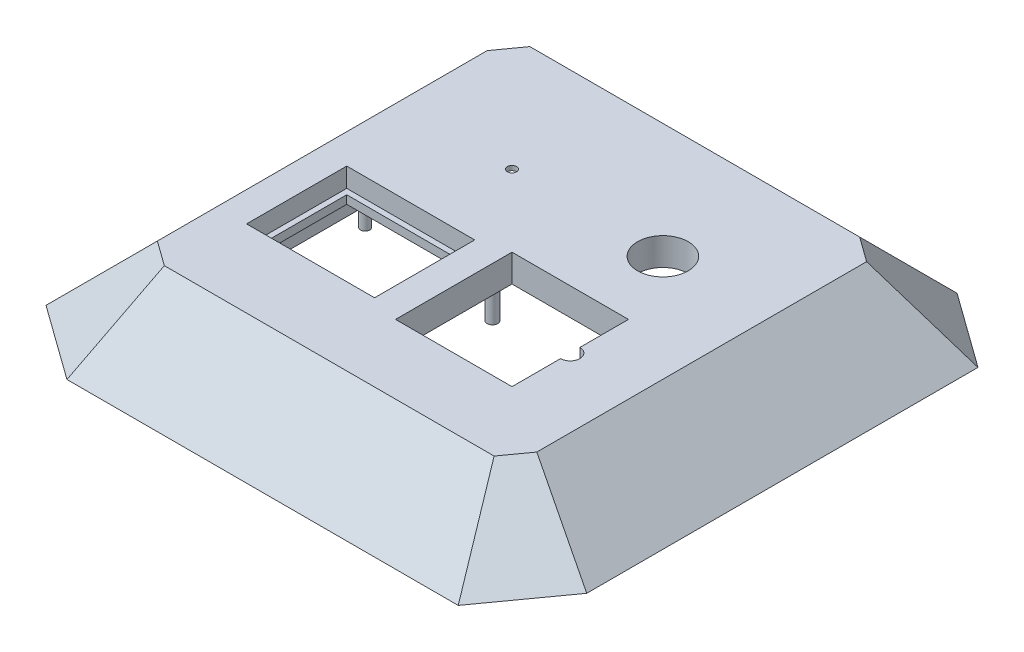
SolidWorks part; units mm, degrees
ref_plane "Front Plane" through (0, 0, 0) normal (0, 0, 1) x (1, 0, 0)
ref_plane "Top Plane" through (0, 0, 0) normal (0, 1, 0) x (1, 0, 0)
ref_plane "Right Plane" through (0, 0, 0) normal (1, 0, 0) x (0, 0, -1)
sketch "Sketch1" plane through (0, 0, 0) normal (0, 1, 0) x (1, 0, 0)
  line L0 (-47.3454, -21.7516) -> (37.6546, -21.7516)
  line L1 (37.6546, -21.7516) -> (49.3368, -5.5181)
  line L2 (49.3368, -5.5181) -> (49.3368, 79.4819)
  line L3 (49.3368, 79.4819) -> (33.1033, 91.1641)
  line L4 (33.1033, 91.1641) -> (-51.8967, 91.1641)
  line L5 (-51.8967, 91.1641) -> (-63.5789, 74.9306)
  line L6 (-63.5789, 74.9306) -> (-63.5789, -10.0694)
  line L7 (-63.5789, -10.0694) -> (-47.3454, -21.7516)
  dimension "D2" = 85
  dimension "D3" = 85
  dimension "D4" = 144.26
  dimension "D5" = 144.26
  dimension "D6" = 85
  dimension "D7" = 144.26
  dimension "D8" = 20
  dimension "D9" = 85
  dimension "D10" = 20
  dimension "D11" = 20
extrude "Boss-Extrude2" add sketch "Sketch1" along normal blind 16
sketch "Sketch4" plane through (0, 0, 0) normal (0, -1, 0) x (1, 0, 0)
  line L16 (-42.1868, 5.7516) -> (-47.5789, 1.8712)
  line L17 (-47.5789, 1.8712) -> (-47.5789, -69.772)
  line L18 (-47.5789, -69.772) -> (-43.6985, -75.1641)
  line L19 (-43.6985, -75.1641) -> (27.9447, -75.1641)
  line L20 (27.9447, -75.1641) -> (33.3368, -71.2838)
  line L21 (33.3368, -71.2838) -> (33.3368, 0.3594)
  line L22 (33.3368, 0.3594) -> (29.4564, 5.7516)
  line L23 (29.4564, 5.7516) -> (-42.1868, 5.7516)
  line L24 (-42.1868, 5.7516) -> (-47.5789, 1.8712)
  line L25 (-47.5789, 1.8712) -> (-47.5789, -69.772)
  line L26 (-47.5789, -69.772) -> (-43.6985, -75.1641)
  line L27 (-43.6985, -75.1641) -> (27.9447, -75.1641)
  line L28 (27.9447, -75.1641) -> (33.3368, -71.2838)
  line L29 (33.3368, -71.2838) -> (33.3368, 0.3594)
  line L30 (33.3368, 0.3594) -> (29.4564, 5.7516)
  line L31 (29.4564, 5.7516) -> (-42.1868, 5.7516)
  dimension "D1" = 16
chamfer "Chamfer1" distance 16 angle 45 8 edges at (-63.5789, 16, -32.4306) (-57.7378, 16, -83.0473) (-9.3967, 16, -91.1641) (41.22, 16, -85.323) (49.3368, 16, -36.9819) (43.4957, 16, 13.6348) (-4.8454, 16, 21.7516) (-55.4621, 16, 15.9105)
extrude "Cut-Extrude3" cut sketch "Sketch4" against normal blind 10
sketch "Sketch6" plane through (0, 16, 0) normal (0, 1, 0) x (1, 0, 0)
  line L0 (33.3368, -0.3594) -> (33.3368, 71.2838) construction
  line L1 (-6.9632, 34.5484) -> (18.3368, 34.5484)
  line L2 (-6.9632, 34.5484) -> (-6.9632, 9.2484)
  line L3 (-6.9632, 9.2484) -> (18.3368, 9.2484)
  line L4 (18.3368, 34.5484) -> (18.3368, 9.2484)
  line L5 (-42.1868, -5.7516) -> (29.4564, -5.7516) construction
  dimension "D1" = 25.3
  dimension "D2" = 25.3
  dimension "D3" = 15
  dimension "D4" = 15
extrude "Cut-Extrude4" cut sketch "Sketch6" against normal up to next
sketch "Sketch7" plane through (0, 10, 0) normal (0, -1, 0) x (1, 0, 0)
  line L0 (18.3368, -9.2484) -> (18.3368, -34.5484) construction
  circle A0 centre (18.3368, -21.8984) radius 2.0981
extrude "Cut-Extrude5" cut sketch "Sketch7" against normal up to next
sketch "Sketch8" plane through (0, 10, 0) normal (0, -1, 0) x (1, 0, 0)
  line L0 (-11.7632, -21.9984) -> (30.1662, -21.9984) construction
  line L1 (-11.7632, -8.8984) -> (24.2368, -8.8984)
  line L2 (-11.7632, -8.8984) -> (-11.7632, -35.0984)
  line L3 (-11.7632, -35.0984) -> (24.2368, -35.0984)
  line L4 (24.2368, -8.8984) -> (24.2368, -35.0984)
  line L5 (6.2368, -8.8984) -> (6.2368, -38.2867) construction
  line L6 (33.3368, -71.2838) -> (33.3368, 0.3594) construction
  line L7 (29.4564, 5.7516) -> (-42.1868, 5.7516) construction
  circle A0 centre (-9.2132, -11.4484) radius 1.15
  circle A1 centre (21.6868, -11.4484) radius 1.15
  circle A2 centre (21.6868, -32.5484) radius 1.15
  circle A3 centre (-9.2132, -32.5484) radius 1.15
  dimension "D3" = 2.3
  dimension "D4" = 2.55
  dimension "D5" = 2.55
  dimension "D6" = 9.1
  dimension "D1" = 36
  dimension "D2" = 26.2
  dimension "D7" = 14.65
extrude "Boss-Extrude3" add sketch "Sketch8" along normal blind 7 contours A0 | A1 | A2 | A3 region at (-9.2132, 10, -11.4484) region at (21.6868, 10, -11.4484) region at (21.6868, 10, -32.5484)
sketch "Sketch9" plane through (0, 10, 0) normal (0, -1, 0) x (1, 0, 0)
  line L2 (-47.5789, 1.8712) -> (-47.5789, -69.772) construction
  line L3 (-43.6985, -75.1641) -> (27.9447, -75.1641) construction
  circle A0 centre (-22.5789, -50.1641) radius 15.65
  dimension "D1" = 25
  dimension "D2" = 25
  dimension "D3" = 31.3
extrude "Cut-Extrude6" cut sketch "Sketch9" against normal blind 5
sketch "Sketch10" plane through (0, 15, 0) normal (0, -1, 0) x (1, 0, 0)
  circle A0 centre (-22.5789, -50.1641) radius 1
  dimension "D1" = 2
extrude "Cut-Extrude7" cut sketch "Sketch10" against normal up to next
sketch "Sketch11" plane through (0, 16, 0) normal (0, 1, 0) x (1, 0, 0)
  line L0 (-14.7144, 21.8984) -> (-6.9632, 21.8984) construction
  line L1 (-14.7144, 35.3984) -> (-39.7144, 35.3984)
  line L2 (-14.7144, 35.3984) -> (-14.7144, 8.3984)
  line L3 (-14.7144, 8.3984) -> (-39.7144, 8.3984)
  line L4 (-39.7144, 35.3984) -> (-39.7144, 8.3984)
  line L5 (-6.9632, 34.5484) -> (-6.9632, 9.2484) construction
  line L6 (-27.2144, 35.3984) -> (-27.2144, 2.0931) construction
  line L7 (-14.7144, 21.8984) -> (-44.3409, 21.8984) construction
  circle A0 centre (-37.5644, 33.2484) radius 1
  circle A1 centre (-16.8644, 33.2484) radius 1
  circle A2 centre (-16.8644, 10.5484) radius 1
  circle A3 centre (-37.5644, 10.5484) radius 1
  dimension "D3" = 2
  dimension "D4" = 2.15
  dimension "D5" = 2.15
  dimension "D1" = 25
  dimension "D2" = 27
extrude "Boss-Extrude4" add sketch "Sketch11" against normal blind 10 contours A0 | A1 | A2 | A3
sketch "Sketch12" plane through (0, 16, 0) normal (0, 1, 0) x (1, 0, 0)
  line L0 (-14.7144, 35.3984) -> (-14.7144, 8.3984) construction
  line L1 (-39.9144, 31.5984) -> (-14.5144, 31.5984)
  line L2 (-39.9144, 31.5984) -> (-39.9144, 12.2384)
  line L3 (-39.9144, 12.2384) -> (-14.5144, 12.2384)
  line L4 (-14.5144, 31.5984) -> (-14.5144, 12.2384)
  line L5 (-39.7144, 35.3984) -> (-39.7144, 8.3984) construction
  line L6 (-14.7144, 35.3984) -> (-39.7144, 35.3984) construction
  line L7 (-14.7144, 8.3984) -> (-39.7144, 8.3984) construction
  dimension "D1" = 0.2
  dimension "D2" = 0.2
  dimension "D3" = 3.8
  dimension "D4" = 3.84
extrude "Cut-Extrude8" cut sketch "Sketch12" against normal through all
sketch "Sketch13" plane through (0, 16, 0) normal (0, 1, 0) x (1, 0, 0)
  line L0 (-14.5144, 31.5984) -> (-39.9144, 31.5984) construction
  line L1 (-41.1144, 32.7984) -> (-13.3144, 32.7984)
  line L2 (-41.1144, 32.7984) -> (-41.1144, 11.0384)
  line L3 (-41.1144, 11.0384) -> (-13.3144, 11.0384)
  line L4 (-13.3144, 32.7984) -> (-13.3144, 11.0384)
  line L5 (-39.9144, 31.5984) -> (-39.9144, 12.2384) construction
  line L6 (-14.5144, 12.2384) -> (-14.5144, 31.5984) construction
  line L7 (-39.9144, 12.2384) -> (-14.5144, 12.2384) construction
  dimension "D1" = 1.2
  dimension "D2" = 1.2
  dimension "D3" = 1.2
  dimension "D4" = 1.2
extrude "Cut-Extrude9" cut sketch "Sketch13" against normal blind 4.2
sketch "Sketch14" plane through (0, 16, 0) normal (0, 1, 0) x (1, 0, 0)
  line L0 (10.2005, 50.1641) -> (-22.5789, 50.1641) construction
  circle A0 centre (10.2005, 50.1641) radius 5.5
extrude "Cut-Extrude10" cut sketch "Sketch14" against normal through all contours A0
